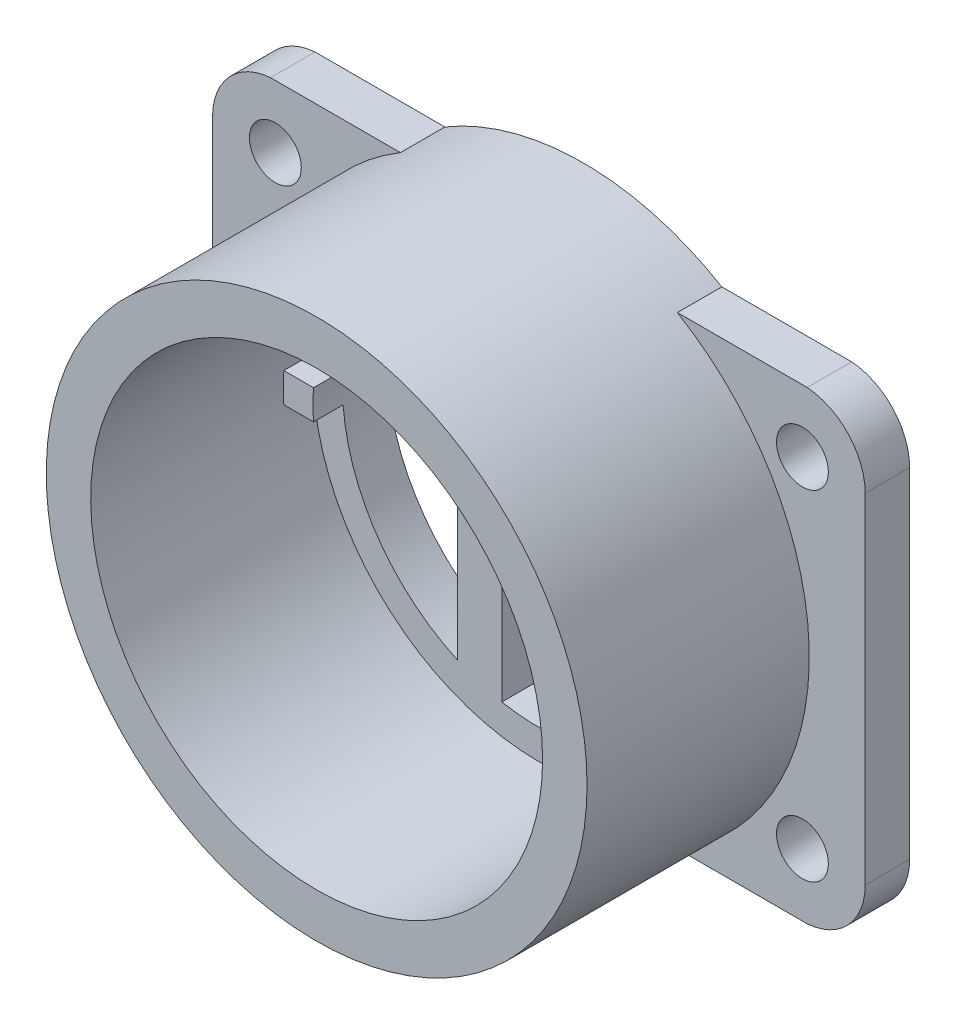
SolidWorks part; units mm, degrees
ref_plane "Front Plane" through (0, 0, 0) normal (0, 0, 1) x (1, 0, 0)
ref_plane "Top Plane" through (0, 0, 0) normal (0, 1, 0) x (1, 0, 0)
ref_plane "Right Plane" through (0, 0, 0) normal (1, 0, 0) x (0, 0, -1)
sketch "Sketch1" plane through (0, 0, 0) normal (0, 0, 1) x (1, 0, 0)
  line L4 (18.1127, 15.675) -> (-18.1127, 15.675)
  line L5 (-22.025, 11.45) -> (-22.025, -11.45)
  line L6 (-18.1127, -15.675) -> (18.1127, -15.675)
  line L7 (22.025, -11.45) -> (22.025, 11.45)
  line L8 (18.1127, 15.675) -> (-18.1127, 15.675)
  line L9 (-22.025, 11.45) -> (-22.025, -11.45)
  line L10 (-18.1127, -15.675) -> (18.1127, -15.675)
  line L11 (22.025, -11.45) -> (22.025, 11.45)
  circle A0 centre (-17.7875, -11.45) radius 1.4 construction
  circle A1 centre (-17.7875, 11.45) radius 1.4 construction
  circle A2 centre (17.7875, 11.45) radius 1.4 construction
  circle A3 centre (17.7875, -11.45) radius 1.4 construction
  arc A4 (-18.1127, 15.675) -> (-22.025, 11.45) centre (-17.7875, 11.45) ccw
  arc A5 (-22.025, -11.45) -> (-18.1127, -15.675) centre (-17.7875, -11.45) ccw
  arc A6 (18.1127, -15.675) -> (22.025, -11.45) centre (17.7875, -11.45) ccw
  arc A7 (22.025, 11.45) -> (18.1127, 15.675) centre (17.7875, 11.45) ccw
  arc A8 (-18.1127, 15.675) -> (-22.025, 11.45) centre (-17.7875, 11.45) ccw
  arc A9 (-22.025, -11.45) -> (-18.1127, -15.675) centre (-17.7875, -11.45) ccw
  arc A10 (18.1127, -15.675) -> (22.025, -11.45) centre (17.7875, -11.45) ccw
  arc A11 (22.025, 11.45) -> (18.1127, 15.675) centre (17.7875, 11.45) ccw
  circle A12 centre (-17.7875, -11.45) radius 1.4
  circle A13 centre (-17.7875, 11.45) radius 1.4
  circle A14 centre (17.7875, 11.45) radius 1.4
  circle A15 centre (17.7875, -11.45) radius 1.4
  circle A16 centre (0, 0) radius 15.25
  circle A17 centre (0, 0) radius 18.25
  circle A18 centre (0, 0) radius 13.25
  dimension "D2" = 30.5
  dimension "D3" = 3
  dimension "D4" = 26.5
  dimension "D1" = 0
extrude "Boss-Extrude1" add sketch "Sketch1" along normal blind 3 contours A17 L8 A8 L9 A9 L10 A12 A13 | L8 A17 L10 A16 | L8 A17 | L10 A17 | A16 | A17 L10 A10 L11 A11 L8 A15 A14 region at (18.268, 0, 0) region at (15.4504, 8.7759, 0) region at (0, 16.7115, 0) region at (-18.268, 0, 0) region at (0, -16.7115, 0) region at (-14.8187, 0, 0)
sketch "Sketch3" plane through (0, 0, 3) normal (0, 0, 1) x (1, 0, 0)
  circle A0 centre (0, 0) radius 18.25
  arc A1 (9.3465, 15.675) -> (-9.3465, 15.675) centre (0, 0) ccw construction
  circle A2 centre (0, 0) radius 15.25
  dimension "D1" = 30.5
extrude "Boss-Extrude2" add sketch "Sketch3" along normal blind 15
sketch "Sketch4" plane through (0, 0, 3) normal (0, 0, 1) x (1, 0, 0)
  line L0 (-15.4939, 15.0131) -> (-12.6325, 13.1712)
  line L1 (-17.7875, 11.45) -> (0, 0) construction
  line L2 (-20.0811, 7.8869) -> (-17.2198, 6.045)
  line L3 (0, 18.25) -> (0, -18.25) construction
  line L4 (-18.25, 0) -> (18.25, 0) construction
  line L5 (15.4939, 15.0131) -> (12.6325, 13.1712)
  line L6 (20.0811, 7.8869) -> (17.2198, 6.045)
  line L7 (20.0811, -7.8869) -> (17.2198, -6.045)
  line L8 (15.4939, -15.0131) -> (12.6325, -13.1712)
  line L9 (-15.4939, -15.0131) -> (-12.6325, -13.1712)
  line L10 (-20.0811, -7.8869) -> (-17.2198, -6.045)
  line L11 (19.5375, 8.7314) -> (16.3081, 8.5752)
  line L12 (-19.2669, 14.3248) -> (-21.0169, 11.6062)
  line L13 (-21.0169, 11.6062) -> (-19.5375, 8.7314)
  line L14 (-19.5375, 8.7314) -> (-16.3081, 8.5752)
  line L15 (-16.3081, 8.5752) -> (-14.5581, 11.2938)
  line L16 (-14.5581, 11.2938) -> (-16.0375, 14.1686)
  line L17 (-16.0375, 14.1686) -> (-19.2669, 14.3248)
  line L18 (16.3081, 8.5752) -> (14.5581, 11.2938)
  line L19 (14.5581, 11.2938) -> (16.0375, 14.1686)
  line L20 (16.0375, 14.1686) -> (19.2669, 14.3248)
  line L21 (19.2669, 14.3248) -> (21.0169, 11.6062)
  line L22 (21.0169, 11.6062) -> (19.5375, 8.7314)
  line L23 (-14.5581, -11.2938) -> (-16.0375, -14.1686)
  line L24 (-16.3081, -8.5752) -> (-14.5581, -11.2938)
  line L25 (-19.5375, -8.7314) -> (-16.3081, -8.5752)
  line L26 (-21.0169, -11.6062) -> (-19.5375, -8.7314)
  line L27 (-19.2669, -14.3248) -> (-21.0169, -11.6062)
  line L28 (-16.0375, -14.1686) -> (-19.2669, -14.3248)
  line L29 (16.3081, -8.5752) -> (14.5581, -11.2938)
  line L30 (19.5375, -8.7314) -> (16.3081, -8.5752)
  line L31 (21.0169, -11.6062) -> (19.5375, -8.7314)
  line L32 (19.2669, -14.3248) -> (21.0169, -11.6062)
  line L33 (16.0375, -14.1686) -> (19.2669, -14.3248)
  line L34 (14.5581, -11.2938) -> (16.0375, -14.1686)
  circle A0 centre (-17.7875, 11.45) radius 4.2375
  arc A1 (-18.1127, 15.675) -> (-22.025, 11.45) centre (-17.7875, 11.45) ccw construction
  arc A2 (-9.3465, 15.675) -> (-9.3465, -15.675) centre (0, 0) ccw construction
  circle A3 centre (0, 0) radius 18.25 construction
  circle A4 centre (0, 0) radius 18.25
  circle A5 centre (17.7875, 11.45) radius 4.2375
  circle A6 centre (17.7875, -11.45) radius 4.2375
  circle A7 centre (-17.7875, -11.45) radius 4.2375
  circle A8 centre (-17.7875, 11.45) radius 2.8 construction
  arc M19 (-9.3465, -15.675) -> (-9.3465, 15.675) centre (0, 0) cw
  line M20 (-9.3465, 15.675) -> (-18.1127, 15.675)
  arc M21 (-18.1127, 15.675) -> (-22.025, 11.45) centre (-17.7875, 11.45) ccw
  arc M23 (-22.025, -11.45) -> (-18.1127, -15.675) centre (-17.7875, -11.45) ccw
  line M24 (-18.1127, -15.675) -> (-9.3465, -15.675)
  dimension "D1" = 5.6
extrude "Boss-Extrude3" [suppressed] add sketch "Sketch4" along normal blind 3 contours A0 L17 L16 L15 L14 L13 L12 M19 M20 M21 | A0 L0 M19 | A0 L2 M19 | A4 A5 L5 | A5 A4 L21 L22 L11 L18 L19 L20 | L6 A5 A4 | A6 L7 A4 | A6 A4 L34 L29 L30 L31 L32 L33 | A6 A4 L8 | A7 L9 M19 | A7 A4 L23 L28 L27 L26 L25 L24 M23 M24 | L10 A7 M19
sketch "Sketch5" plane through (0, 0, 3) normal (0, 0, 1) x (1, 0, 0)
  line L1 (-15.25, -1) -> (15.25, -1)
  line L2 (-15.25, -1) -> (-15.25, 1)
  line L3 (-15.25, 1) -> (15.25, 1)
  line L4 (15.25, -1) -> (15.25, 1)
  line L5 (-15.25, -1) -> (15.25, 1) construction
  line L6 (-15.25, 1) -> (15.25, -1) construction
  circle A0 centre (0, 0) radius 15.25 construction
  circle A1 centre (0, 0) radius 13.25 construction
  circle A2 centre (0, 0) radius 13.25
  point P0 (0, 0)
  circle M3 centre (0, 0) radius 13.25
  circle M4 centre (0, 0) radius 15.25
  dimension "D1" = 2
extrude "Boss-Extrude4" add sketch "Sketch5" along normal blind 2 contours L3 L1 M4 M3 | L3 L1 M3 M4 region at (-14.2382, 0, 3) region at (14.2382, 0, 3)
sketch "Sketch6" plane through (0, 0, 0) normal (0, 0, -1) x (-1, 0, 0)
  line L0 (0, 13.25) -> (0, -13.25) construction
  line L1 (-4, 12.6318) -> (-4, -12.6318) construction
  line L2 (5.5, -13.012) -> (2.5, -13.012)
  line L3 (-5.5, -13.012) -> (-2.5, -13.012)
  line L4 (-5.5, -13.012) -> (-5.5, 13.012)
  line L5 (-5.5, 13.012) -> (-2.5, 13.012)
  line L6 (-2.5, -13.012) -> (-2.5, 13.012)
  line L7 (-5.5, -13.012) -> (-2.5, 13.012) construction
  line L8 (-5.5, 13.012) -> (-2.5, -13.012) construction
  line L9 (2.5, -13.012) -> (2.5, 13.012)
  line L10 (5.5, 13.012) -> (2.5, 13.012)
  line L11 (5.5, -13.012) -> (5.5, 13.012)
  circle A0 centre (0, 0) radius 13.25 construction
  circle A1 centre (0, 0) radius 13.25
  point P7 (-4, 0)
  circle M24 centre (0, 0) radius 13.25
  dimension "D1" = 4
  dimension "D2" = 3
extrude "Boss-Extrude5" add sketch "Sketch6" against normal up to surface (3 mm away) contours L6 L4 M24 | L11 L9 M24 region at (-3.9811, 0, 0) region at (3.9811, 0, 0) up to face at (0, 7.625, 3)
sketch "Sketch7" plane through (0, 0, 3) normal (0, 0, 1) x (1, 0, 0)
  circle A0 centre (-17.7875, 11.45) radius 1.75
  circle A1 centre (17.7875, 11.45) radius 1.75
  circle A2 centre (17.7875, -11.45) radius 1.75
  circle A3 centre (-17.7875, -11.45) radius 1.75
  dimension "D1" = 3.5
extrude "Cut-Extrude1" cut sketch "Sketch7" against normal up to next
